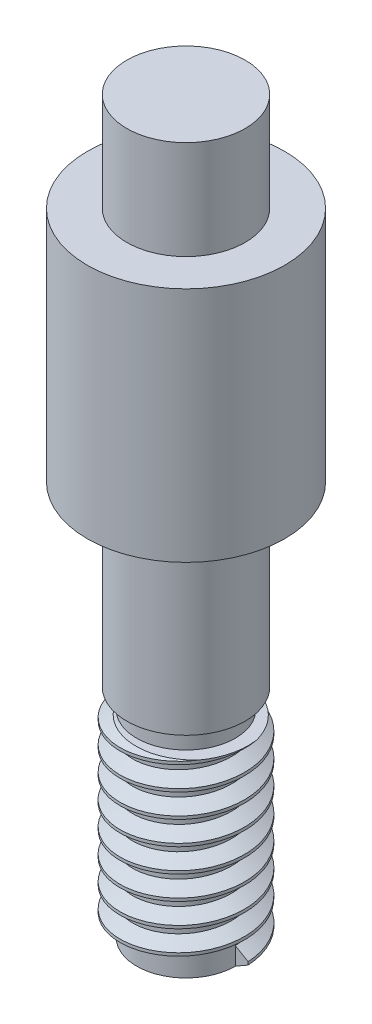
SolidWorks part; units mm, degrees
ref_plane "前视基准面" through (0, 0, 0) normal (0, 0, 1) x (1, 0, 0)
ref_plane "上视基准面" through (0, 0, 0) normal (0, 1, 0) x (1, 0, 0)
ref_plane "右视基准面" through (0, 0, 0) normal (1, 0, 0) x (0, 0, -1)
sketch "草图1" plane through (0, 0, 0) normal (0, 0, 1) x (1, 0, 0)
  line L0 (0, 0) -> (0, 18.5)
  line L1 (0, 18.5) -> (-1.5, 18.5)
  line L2 (-1.5, 18.5) -> (-1.5, 16)
  line L3 (-1.5, 16) -> (-2.5, 16)
  line L4 (-2.5, 16) -> (-2.5, 10)
  line L5 (-2.5, 10) -> (-1.5, 10)
  line L6 (-1.5, 10) -> (-1.5, 0)
  line L7 (-1.5, 0) -> (0, 0)
  dimension "D1" = 1.5
  dimension "D2" = 2.5
  dimension "D3" = 1.5
  dimension "D4" = 2.5
  dimension "D5" = 6
  dimension "D6" = 10
revolve "旋转1" add sketch "草图1" angle 360 about L0
sketch "草图5" plane through (0, 10, 0) normal (0, -1, 0) x (1, 0, 0)
  circle A0 centre (0, 0) radius 1.5
  circle A1 centre (0, 0) radius 1.25
  dimension "D1" = 3
  dimension "D2" = 0.25
extrude "切除-拉伸2" cut sketch "草图5" along normal through all from offset 4.5
thread "螺纹线2" pitch 0.6 method extrude profile "螺纹线轮廓4" start angle 0, offset 0, length 5, pitch 0.6, diameter 2.5
ref_plane "基准面7" through (1.25, 0, 0) normal (0, 0, 1) x (1, 0, 0)
sketch "螺纹线轮廓4" plane through (1.25, 0, 0) normal (0, 0, 1) x (1, 0, 0)
  line L0 (0, 0) -> (0, 0.6) construction
  line L1 (0, 0) -> (0.3248, 0.1875)
  line L2 (0.3248, 0.1875) -> (0.3248, 0.2625)
  line L3 (0.3248, 0.2625) -> (0, 0.45)
  line L4 (0.3248, 0.225) -> (0, 0.225) construction
  line L11 (0, 0) -> (0, 0.45)
  point P2 (0, 0)
  dimension "Pitch" = 0.6
  dimension "Profile_Angle" = 60
  dimension "Profile_Land" = 0.075
  dimension "Profile_Height" = 0.3248
sketch "草图36" plane through (0, 5.5, 0) normal (0, -1, 0) x (1, 0, 0)
  circle A0 centre (0, 0) radius 1.25
  circle A1 centre (0, 0) radius 2.1172
extrude "切除-拉伸3" cut sketch "草图36" along normal blind 0.5
